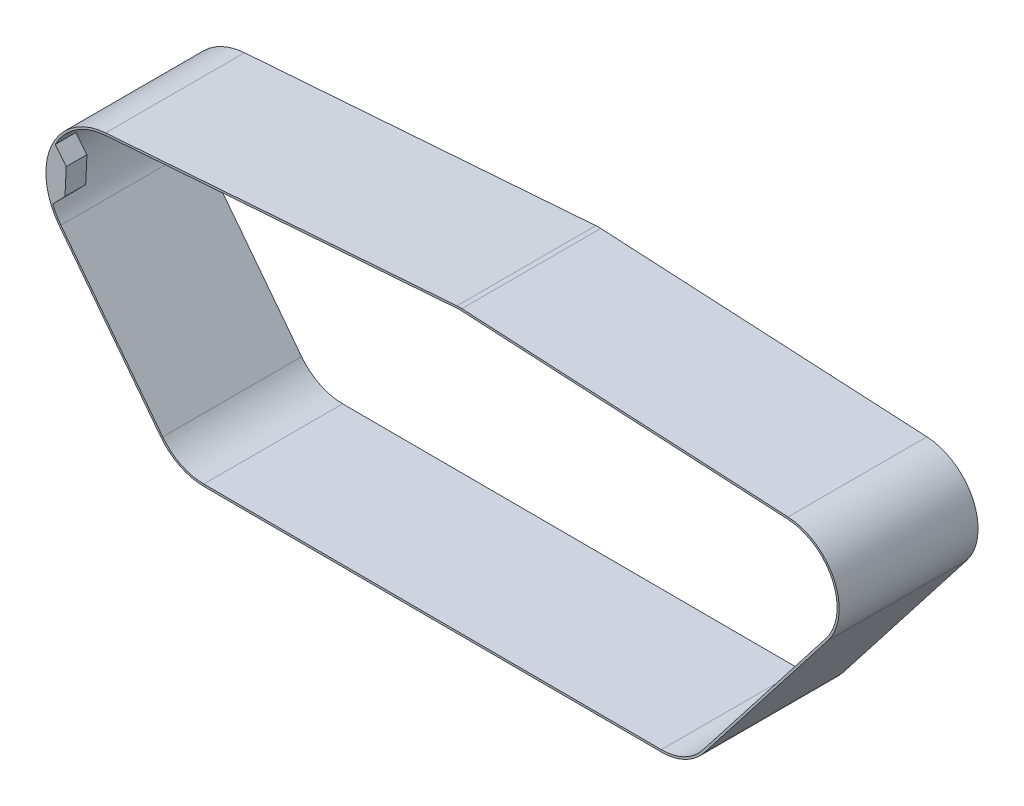
SolidWorks part; units mm, degrees
ref_plane "Front Plane" through (0, 0, 0) normal (0, 0, 1) x (1, 0, 0)
ref_plane "Top Plane" through (0, 0, 0) normal (0, 1, 0) x (1, 0, 0)
ref_plane "Right Plane" through (0, 0, 0) normal (1, 0, 0) x (0, 0, -1)
sketch "Sketch2" plane through (0, 0, 0) normal (0, 0, 1) x (1, 0, 0)
  line L0 (0, 0) -> (1, 0) construction
  line L1 (0, 0) -> (0, 1) construction
  line L2 (-1.551, 21.0429) -> (117.315, 29.804)
  line L3 (118.91, 29.8203) -> (229.2625, 23.9536)
  line L4 (242.2162, -4.4327) -> (200.3827, -58.1721)
  line L5 (186.4458, -64.9609) -> (31.6219, -64.5311)
  line L6 (17.7184, -57.6592) -> (-16.727, -12.8615)
  arc A0 (-16.727, -12.8615) -> (-1.551, 21.0429) centre (0, 0) cw
  arc A1 (117.315, 29.804) -> (118.91, 29.8203) centre (118.2411, 17.238) cw
  arc A2 (229.2625, 23.9536) -> (242.2162, -4.4327) centre (228.3281, 6.3784) cw
  arc A3 (200.3827, -58.1721) -> (186.4458, -64.9609) centre (186.4947, -47.3609) cw
  arc A4 (31.6219, -64.5311) -> (17.7184, -57.6592) centre (31.6707, -46.9312) cw
extrude "Extrude-Thin1" add sketch "Sketch2" along normal mid plane 47 thin thin type one direction wall 0.7
sketch "Sketch3" plane through (0, 0, 23.5) normal (0, 0, 1) x (1, 0, 0)
  line L4 (-19.6673, -8.1751) -> (-15.3426, -3.7742)
  line L5 (-14.9214, 5.1955) -> (-18.8146, 9.9823)
  line L6 (-19.6673, -8.1751) -> (-15.3426, -3.7742) construction
  line L7 (-14.9214, 5.1955) -> (-18.8146, 9.9823) construction
  line L11 (-15.3426, -3.7742) -> (-14.9214, 5.1955)
  line L12 (-14.9214, 5.1955) -> (-18.8146, 9.9823)
  line L13 (-15.3426, -3.7742) -> (-19.6673, -8.1751)
  line L14 (-19.6673, -8.1751) -> (-20.1302, -8.3675)
  line L15 (-18.8146, 9.9823) -> (-19.3668, 10.0083)
  line L16 (-17.0044, -13.0749) -> (17.4409, -57.8726)
  line L17 (117.2892, 30.153) -> (-1.5767, 21.392)
  line L18 (229.281, 24.3031) -> (118.9286, 30.1698)
  line L19 (200.6589, -58.3871) -> (242.4924, -4.6477)
  line L20 (31.6209, -64.8811) -> (186.4448, -65.3109)
  line L21 (-17.0044, -13.0749) -> (17.4409, -57.8726) construction
  line L22 (117.2892, 30.153) -> (-1.5767, 21.392) construction
  line L23 (229.281, 24.3031) -> (118.9286, 30.1698) construction
  line L24 (200.6589, -58.3871) -> (242.4924, -4.6477) construction
  line L25 (31.6209, -64.8811) -> (186.4448, -65.3109) construction
  arc A2 (-14.9214, 5.1955) -> (-15.3426, -3.7742) centre (0, 0) ccw
  arc A3 (-14.9214, 5.1955) -> (-15.3426, -3.7742) centre (0, 0) ccw construction
  arc A8 (-1.6024, 21.741) -> (-17.2819, -13.2882) centre (0, 0) ccw construction
  arc A9 (-19.3668, 10.0083) -> (-20.1302, -8.3675) centre (0, 0) ccw
  arc A13 (-1.5767, 21.392) -> (-17.0044, -13.0749) centre (0, 0) ccw
  arc A14 (118.9286, 30.1698) -> (117.2892, 30.153) centre (118.2411, 17.238) ccw
  arc A15 (242.4924, -4.6477) -> (229.281, 24.3031) centre (228.3281, 6.3784) ccw
  arc A16 (186.4448, -65.3109) -> (200.6589, -58.3871) centre (186.4947, -47.3609) ccw
  arc A17 (17.4409, -57.8726) -> (31.6209, -64.8811) centre (31.6707, -46.9312) ccw
  arc A18 (-1.5767, 21.392) -> (-17.0044, -13.0749) centre (0, 0) ccw construction
  arc A19 (118.9286, 30.1698) -> (117.2892, 30.153) centre (118.2411, 17.238) ccw construction
  arc A20 (242.4924, -4.6477) -> (229.281, 24.3031) centre (228.3281, 6.3784) ccw construction
  arc A21 (186.4448, -65.3109) -> (200.6589, -58.3871) centre (186.4947, -47.3609) ccw construction
  arc A22 (17.4409, -57.8726) -> (31.6209, -64.8811) centre (31.6707, -46.9312) ccw construction
  dimension "D1" = 0.8
  dimension "D2" = 0.35
extrude "Boss-Extrude1" add sketch "Sketch3" against normal blind 7
